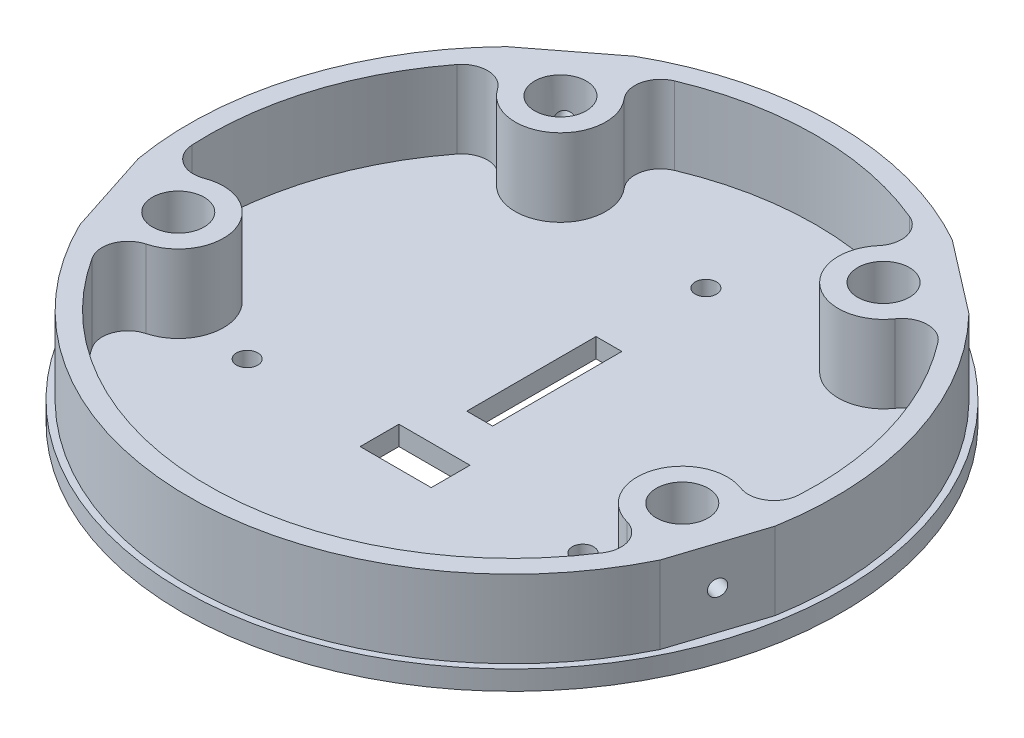
SolidWorks part; units mm, degrees
material "3.0205 (EN-AW 1200)"
ref_plane "Спереди" through (0, 0, 0) normal (0, 0, 1) x (1, 0, 0)
ref_plane "Сверху" through (0, 0, 0) normal (0, 1, 0) x (1, 0, 0)
ref_plane "Справа" through (0, 0, 0) normal (1, 0, 0) x (0, 0, -1)
other "Configuration Table"
sketch "Эскиз1" plane through (0, 0, 0) normal (0, 1, 0) x (1, 0, 0)
  circle A0 centre (0, 0) radius 51
  dimension "D1" = 102
extrude "Бобышка-Вытянуть1" add sketch "Эскиз1" along normal blind 3
sketch "Эскиз2" plane through (0, 3, 0) normal (0, 1, 0) x (1, 0, 0)
  circle A0 centre (0, 0) radius 50
  circle A1 centre (0, 0) radius 47
  circle A2 centre (0, 0) radius 51
  circle A3 centre (0, 0) radius 51
  dimension "D2" = 100
  dimension "D3" = 94
  dimension "D1" = 0
extrude "Бобышка-Вытянуть2" add sketch "Эскиз2" along normal blind 12 contours A0 A1 region at (-48.5858, 3, 0)
sketch "Эскиз5" plane through (0, 3, 0) normal (0, 1, 0) x (1, 0, 0)
  line L0 (0, 0) -> (50000, 0) construction
  line L1 (0, 0) -> (0, 50000) construction
  circle A0 centre (0, 0) radius 30 construction
  circle A1 centre (0, 30) radius 1.65
  dimension "D1" = 60
  dimension "D2" = 3.3
extrude "Вырез-Вытянуть1" cut sketch "Эскиз5" against normal blind 10
pattern_circular "Круговой массив1" count 3 over 360 about axis through (0, 15, 0) along (0, -1, 0) of "Вырез-Вытянуть1" reverse direction yes
sketch "Эскиз6" plane through (0, 3, 0) normal (0, 1, 0) x (1, 0, 0)
  line L0 (0, -1000) -> (0, 49000) construction
  line L1 (-1025.9808, -15) -> (48974.0192, -15) construction
  line L2 (-2, -5) -> (2, -5)
  line L3 (-2, -5) -> (-2, 15)
  line L4 (-2, 15) -> (2, 15)
  line L5 (2, -5) -> (2, 15)
  line L6 (-2, -5) -> (2, 15) construction
  line L7 (-2, 15) -> (2, -5) construction
  line L8 (-5.5, -12) -> (5.5, -12)
  line L9 (-5.5, -12) -> (-5.5, -18)
  line L10 (-5.5, -18) -> (5.5, -18)
  line L11 (5.5, -12) -> (5.5, -18)
  line L12 (-5.5, -12) -> (5.5, -18) construction
  line L13 (-5.5, -18) -> (5.5, -12) construction
  circle A1 centre (0, 30) radius 1.65 construction
  point P1 (0, 5)
  point P10 (0, -15)
  dimension "D3" = 15
  dimension "D1" = 4
  dimension "D2" = 20
  dimension "D4" = 6
  dimension "D5" = 11
extrude "Вырез-Вытянуть2" cut sketch "Эскиз6" against normal blind 10
sketch "Эскиз7" plane through (0, 3, 0) normal (0, 1, 0) x (1, 0, 0)
  line L0 (-1000, 0) -> (49000, 0) construction
  line L1 (0, -1000) -> (0, 49000) construction
  line L2 (-39, -12.6491) -> (39, -12.6491) construction
  line L3 (-25, 32.4962) -> (25, 32.4962) construction
  circle A0 centre (0, 0) radius 41 construction
  circle A1 centre (-39, -12.6491) radius 4
  circle A2 centre (39, -12.6491) radius 4
  circle A3 centre (-39, -12.6491) radius 7
  circle A4 centre (39, -12.6491) radius 7
  circle A5 centre (-25, 32.4962) radius 4
  circle A6 centre (25, 32.4962) radius 4
  circle A7 centre (-25, 32.4962) radius 7
  circle A8 centre (25, 32.4962) radius 7
  dimension "D1" = 82
  dimension "D2" = 8
  dimension "D3" = 8
  dimension "D5" = 14
  dimension "D6" = 14
  dimension "D7" = 8
  dimension "D8" = 8
  dimension "D10" = 14
  dimension "D11" = 14
  dimension "D4" = 78
  dimension "D9" = 50
extrude "Бобышка-Вытянуть3" add sketch "Эскиз7" along normal blind 12
sketch "Эскиз8" plane through (0, 15, 0) normal (0, 1, 0) x (1, 0, 0)
  line L0 (0, 0) -> (-39, -12.6491) construction
  line L1 (-49.2614, -8.5622) -> (-44.9093, -21.9808)
  line L2 (0, 0) -> (-25, 32.4962) construction
  line L3 (-35.7733, 34.9323) -> (-24.5925, 43.534)
  circle A1 centre (0, 0) radius 50 construction
  arc A2 (-24.5925, 43.534) -> (-35.7733, 34.9323) centre (0, 0) ccw
  arc A3 (-49.2614, -8.5622) -> (-44.9093, -21.9808) centre (0, 0) ccw
  dimension "D1" = 49.5
  dimension "D2" = 49.5
extrude "Вырез-Вытянуть3" cut sketch "Эскиз8" against normal blind 12
fillet "Скругление1" radius 4 8 edges at (45.7465, 9, 10.7823) (43.3665, 9, 18.1202) (25.5048, 9, -39.4779) (31.619, 9, -34.7741) (-31.619, 9, -34.7741) (-25.5048, 9, -39.4779) (-45.7465, 9, 10.7823) (-43.3665, 9, 18.1202)
mirror "Зеркальное отражение1" about plane through (0, 0, 0) normal (1, 0, 0) of "Вырез-Вытянуть3"
sketch "Эскиз9" plane through (-47.0854, 0, 15.2715) normal (-0.9512, 0, 0.3085) x (0.3085, 0, 0.9512)
  line L0 (0, 0) -> (0, 15) construction
  line L1 (7.0534, 15) -> (-7.0534, 15) construction
  circle A0 centre (0, 9) radius 1.25
  dimension "D1" = 2.5
  dimension "D2" = 6
extrude "Вырез-Вытянуть4" cut sketch "Эскиз9" against normal blind 10
sketch "Эскиз10" plane through (-30.1829, 0, -39.2332) normal (-0.6098, 0, -0.7926) x (-0.7926, 0, 0.6098)
  line L0 (0, 0) -> (0, 15) construction
  line L1 (7.0534, 15) -> (-7.0534, 15) construction
  circle A0 centre (0, 9) radius 1.25
  dimension "D1" = 6
  dimension "D2" = 2.5
extrude "Вырез-Вытянуть5" cut sketch "Эскиз10" against normal blind 10
mirror "Зеркальное отражение2" about plane through (0, 0, 0) normal (1, 0, 0) of "Вырез-Вытянуть4", "Вырез-Вытянуть5"
